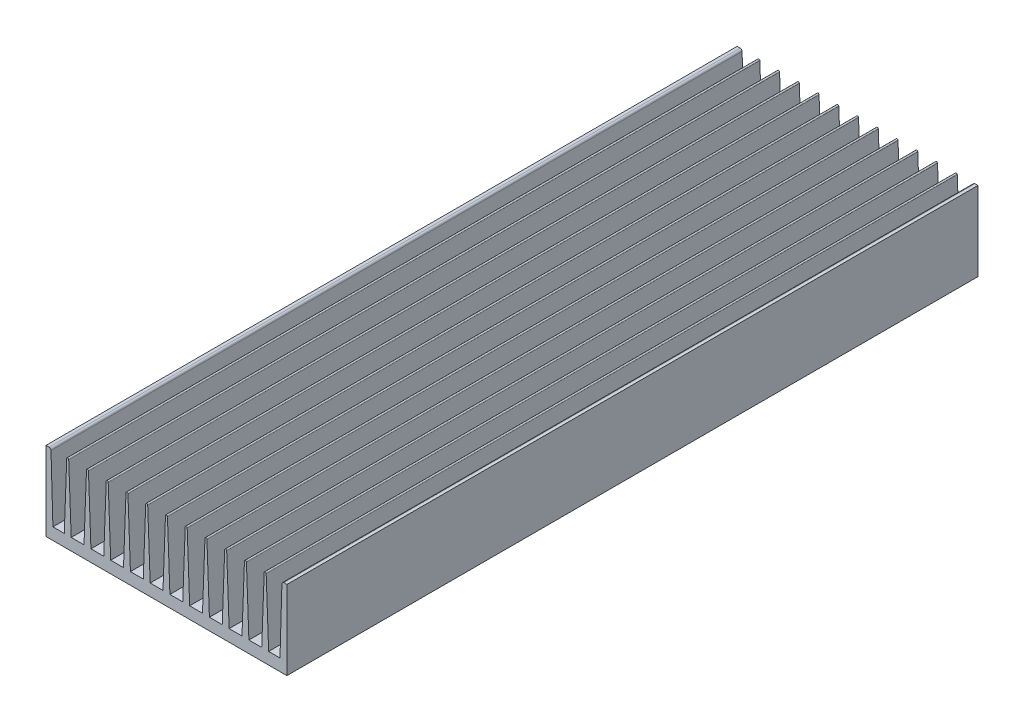
SolidWorks part; units mm, degrees
ref_plane "Спереди" through (0, 0, 0) normal (0, 0, 1) x (1, 0, 0)
ref_plane "Сверху" through (0, 0, 0) normal (0, 1, 0) x (1, 0, 0)
ref_plane "Справа" through (0, 0, 0) normal (1, 0, 0) x (0, 0, -1)
sketch "Эскиз1" plane through (0, 0, 0) normal (0, 0, 1) x (1, 0, 0)
  line L0 (0, 40) -> (1.529, 40)
  line L1 (0, 0) -> (122, 0)
  line L2 (2.5285, 39.0294) -> (3.5, 6)
  line L3 (0, 40) -> (0, 0)
  line L4 (122, 40) -> (122, 0)
  line L5 (61, 63.7127) -> (61, -22.2582) construction
  line L8 (122, 40) -> (120.471, 40)
  line L9 (119.4715, 39.0294) -> (118.5, 6)
  line L10 (3.5, 6) -> (118.5, 6)
  arc A0 (1.529, 40) -> (2.5285, 39.0294) centre (1.529, 39) cw
  arc A2 (120.471, 40) -> (119.4715, 39.0294) centre (120.471, 39) ccw
  point P18 (119.5, 40)
  dimension "D9" = 1
  dimension "D1" = 122
  dimension "D2" = 6
  dimension "D3" = 40
  dimension "D4" = 3.5
  dimension "D7" = 2.5
extrude "Вытянуть1" add sketch "Эскиз1" along normal blind 350
sketch "Эскиз2" plane through (0, 0, 350) normal (0, 0, 1) x (1, 0, 0)
  line L0 (118.5, 6) -> (3.5, 6) construction
  line L1 (10.5, 39.5) -> (9.25, 6)
  line L2 (11, 39.5) -> (11, 22.5548) construction
  line L3 (11.5, 39.5) -> (12.75, 6)
  line L4 (9.25, 6) -> (12.75, 6)
  line L6 (0, 40) -> (0, 0) construction
  arc A0 (10.5, 39.5) -> (11.5, 39.5) centre (11, 39.5) cw
  dimension "D1" = 34
  dimension "D3" = 0.5
  dimension "D2" = 3.5
  dimension "D4" = 11
  dimension "D5" = 1
extrude "Вытянуть3" add sketch "Эскиз2" against normal blind 350
pattern_curve "Кривая1" of "Вытянуть3" along edge at (61, 0, 0) parameters "D1"=11, "D3"=10, "D2"=1, "D4"=50
sketch "Эскиз3" plane through (0, 0, 0) normal (0, -1, 0) x (1, 0, 0)
  line L0 (-14.0506, 342) -> (137.5079, 342) construction
  line L1 (0, 350) -> (122, 350) construction
  line L2 (0, 350) -> (0, 0) construction
  line L3 (-46.7511, 175) -> (151.4312, 175) construction
  line L4 (0, 0) -> (122, 0) construction
  circle A0 centre (26, 342) radius 2.25
  circle A1 centre (96, 342) radius 2.25
  circle A2 centre (96, 8) radius 2.25
  circle A3 centre (26, 8) radius 2.25
  dimension "D2" = 70
  dimension "D4" = 4.5
  dimension "D1" = 8
  dimension "D3" = 26
extrude "Вырез-Вытянуть1" cut sketch "Эскиз3" against normal blind 6
sketch "Эскиз4" plane through (0, 0, 0) normal (0, -1, 0) x (1, 0, 0)
  line L0 (55, 25) -> (90, 25) construction
  line L1 (55, 85) -> (90, 85) construction
  line L2 (55, 25) -> (55, 85) construction
  line L3 (90, 25) -> (90, 85) construction
  line L4 (0, 0) -> (122, 0) construction
  line L5 (0, 350) -> (0, 0) construction
  line L6 (90, 25) -> (109.4297, 25) construction
  line L7 (13.6094, 115) -> (112, 115) construction
  line L8 (55, 85) -> (55, 255) construction
  line L9 (112, 25) -> (112, 115) construction
  line L10 (96, 342) -> (96, 283.296) construction
  line L11 (122, 350) -> (122, 0) construction
  circle A0 centre (55, 25) radius 1.6
  circle A1 centre (90, 25) radius 1.6
  circle A2 centre (55, 85) radius 1.6
  circle A3 centre (90, 85) radius 1.6
  circle A4 centre (112, 25) radius 2.25
  circle A5 centre (55, 115) radius 2.1
  circle A6 centre (84.5, 115) radius 1.6
  circle A7 centre (112, 107) radius 2.25
  circle A9 centre (96, 320) radius 2.25
  circle A10 centre (96, 295) radius 2.25
  circle A11 centre (55, 140) radius 1.1
  circle A12 centre (55, 166) radius 1.1
  circle A13 centre (55, 195) radius 1.6
  circle A14 centre (84.5, 255) radius 1.6
  dimension "D1" = 3.2
  dimension "D6" = 4.5
  dimension "D9" = 4.2
  dimension "D13" = 25
  dimension "D14" = 3.2
  dimension "D15" = 2.2
  dimension "D16" = 195
  dimension "D17" = 140
  dimension "D18" = 26
  dimension "D11" = 82
  dimension "D20" = 37.5
  dimension "D10" = 37.5
  dimension "D2" = 25
  dimension "D3" = 55
  dimension "D4" = 35
  dimension "D5" = 60
  dimension "D7" = 112
  dimension "D8" = 115
  dimension "D12" = 295
  dimension "D19" = 255
extrude "Вырез-Вытянуть2" cut sketch "Эскиз4" against normal blind 6
cosmetic thread "Условное изображение резьбы1" parameters "D1"=6, "D2"=4
cosmetic thread "Условное изображение резьбы2" parameters "D1"=6, "D2"=4
cosmetic thread "Условное изображение резьбы3" parameters "D1"=6, "D2"=4
cosmetic thread "Условное изображение резьбы4" parameters "D1"=6, "D2"=4
cosmetic thread "Условное изображение резьбы5" parameters "D1"=6, "D2"=4
cosmetic thread "Условное изображение резьбы6" parameters "D1"=6, "D2"=4
cosmetic thread "Условное изображение резьбы7" parameters "D1"=6, "D2"=4
cosmetic thread "Условное изображение резьбы8" parameters "D1"=6, "D2"=3
cosmetic thread "Условное изображение резьбы9" parameters "D1"=6, "D2"=3
cosmetic thread "Условное изображение резьбы10" parameters "D1"=6, "D2"=5
